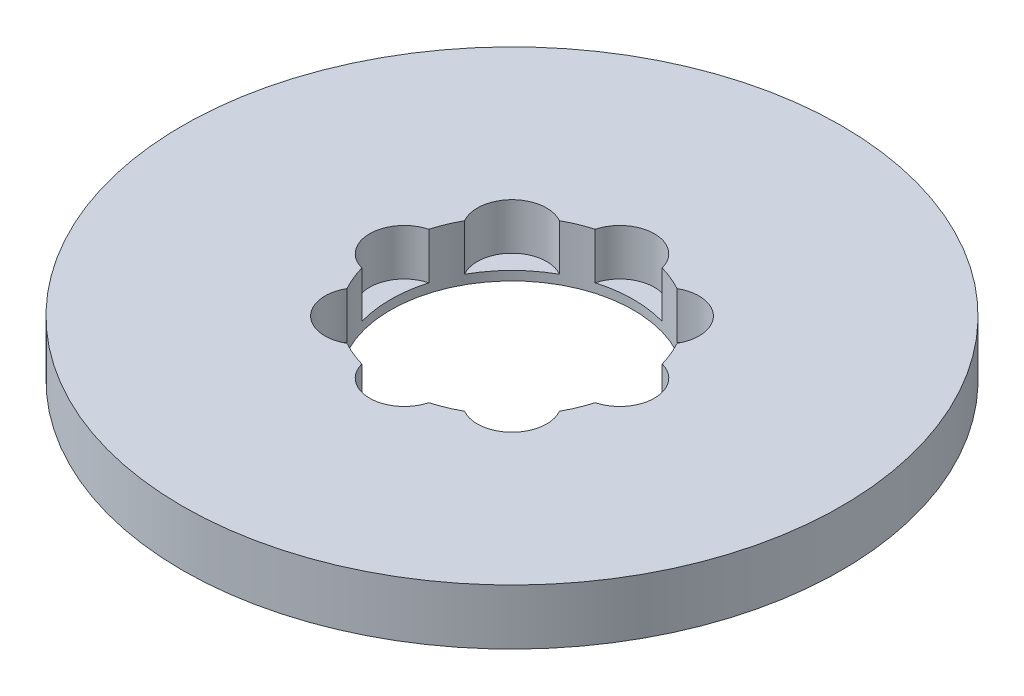
SolidWorks part; units mm, degrees
ref_plane "Front Plane" through (0, 0, 0) normal (0, 0, 1) x (1, 0, 0)
ref_plane "Top Plane" through (0, 0, 0) normal (0, 1, 0) x (1, 0, 0)
ref_plane "Right Plane" through (0, 0, 0) normal (1, 0, 0) x (0, 0, -1)
sketch "Sketch1" plane through (0, 0, 0) normal (0, 1, 0) x (1, 0, 0)
  circle A0 centre (0, 0) radius 95
  dimension "FLANGE_OD" = 190
extrude "Boss-Extrude1" add sketch "Sketch1" along normal blind 16
sketch "Sketch2" plane through (0, 0, 0) normal (0, 1, 0) x (1, 0, 0)
  circle A0 centre (0, 0) radius 35
  dimension "BORE_D" = 70
extrude "Cut-Extrude1" cut sketch "Sketch2" along normal through all
sketch "Sketch3" plane through (0, 16, 0) normal (0, 1, 0) x (1, 0, 0)
  circle A0 centre (0, 0) radius 31.0569 construction
  circle A1 centre (-31.0569, 0) radius 10
  dimension "BOLT_D" = 20
  dimension "BOLT_PCD" = 62.1137
extrude "Cut-Extrude2" cut sketch "Sketch3" against normal blind 13.3699
pattern_circular "CirPattern1" count 8 over 360 about axis through (0, 0, 0) along (0, 1, 0) of "Cut-Extrude2"
